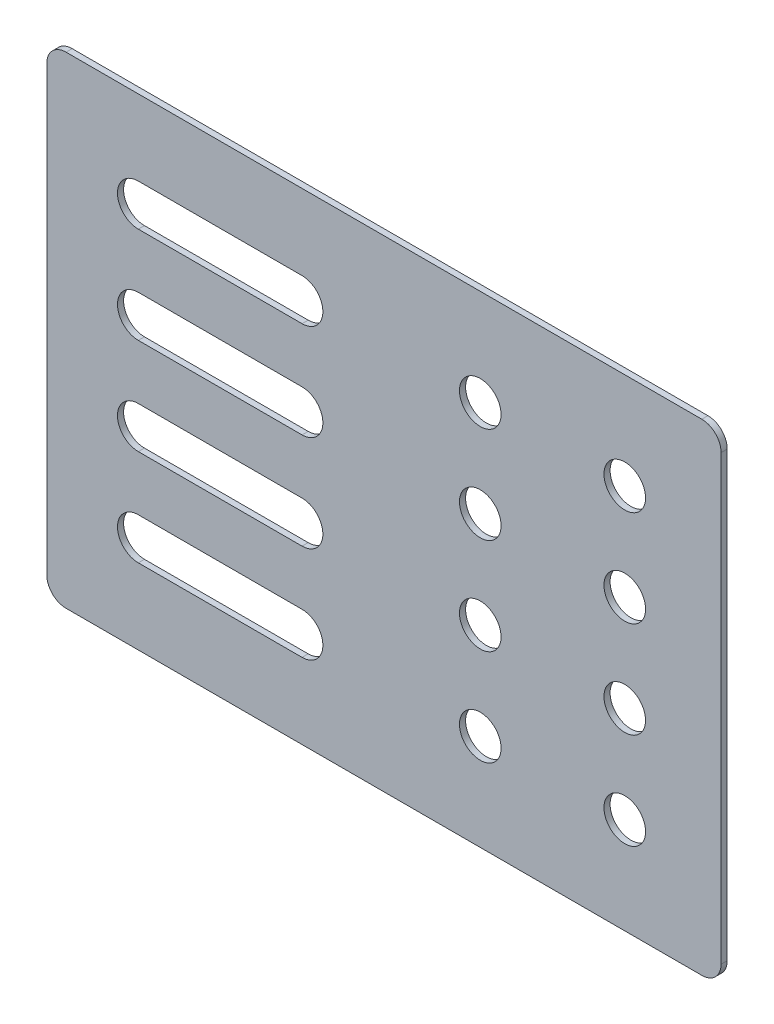
SolidWorks part; units mm, degrees
ref_plane "Front Plane" through (0, 0, 0) normal (0, 0, 1) x (1, 0, 0)
ref_plane "Top Plane" through (0, 0, 0) normal (0, 1, 0) x (1, 0, 0)
ref_plane "Right Plane" through (0, 0, 0) normal (1, 0, 0) x (0, 0, -1)
sketch "Sketch1" plane through (0, 0, 0) normal (0, 0, 1) x (1, 0, 0)
  line L0 (9.5, -10) -> (26.5, -10) construction
  line L1 (70, 0) -> (0, 0)
  line L2 (70, 0) -> (70, -50)
  line L3 (70, -50) -> (0, -50)
  line L4 (0, 0) -> (0, -50)
  line L9 (9.5, -7.84) -> (26.5, -7.84)
  line L12 (9.5, -12.16) -> (26.5, -12.16)
  line L13 (9.5, -22.16) -> (26.5, -22.16)
  line L14 (9.5, -17.84) -> (26.5, -17.84)
  line L15 (9.5, -20) -> (26.5, -20) construction
  line L16 (9.5, -32.16) -> (26.5, -32.16)
  line L17 (9.5, -27.84) -> (26.5, -27.84)
  line L18 (9.5, -30) -> (26.5, -30) construction
  line L19 (9.5, -42.16) -> (26.5, -42.16)
  line L20 (9.5, -37.84) -> (26.5, -37.84)
  line L21 (9.5, -40) -> (26.5, -40) construction
  circle A0 centre (45, -10) radius 2.16
  circle A1 centre (60, -10) radius 2.16
  circle A2 centre (20, -10) radius 2.16
  circle A3 centre (20, -20) radius 2.16
  circle A4 centre (45, -20) radius 2.16
  circle A5 centre (60, -20) radius 2.16
  circle A6 centre (20, -30) radius 2.16
  circle A7 centre (45, -30) radius 2.16
  circle A8 centre (60, -30) radius 2.16
  circle A9 centre (20, -40) radius 2.16
  circle A10 centre (45, -40) radius 2.16
  circle A11 centre (60, -40) radius 2.16
  circle A20 centre (45, -10) radius 3.9624 construction
  circle A21 centre (45, -20) radius 3.9624 construction
  arc A22 (9.5, -7.84) -> (9.5, -12.16) centre (9.5, -10) ccw
  arc A23 (26.5, -12.16) -> (26.5, -7.84) centre (26.5, -10) ccw
  arc A24 (9.5, -17.84) -> (9.5, -22.16) centre (9.5, -20) ccw
  arc A25 (26.5, -22.16) -> (26.5, -17.84) centre (26.5, -20) ccw
  arc A26 (9.5, -27.84) -> (9.5, -32.16) centre (9.5, -30) ccw
  arc A27 (26.5, -32.16) -> (26.5, -27.84) centre (26.5, -30) ccw
  arc A28 (9.5, -37.84) -> (9.5, -42.16) centre (9.5, -40) ccw
  arc A29 (26.5, -42.16) -> (26.5, -37.84) centre (26.5, -40) ccw
  point P8 (18, -10)
  point P40 (18, -20)
  point P47 (18, -30)
  point P54 (18, -40)
  dimension "D5" = 4.32
  dimension "D11" = 7.9248
  dimension "D1" = 10
  dimension "D2" = 15
  dimension "D3" = 70
  dimension "D4" = 10
  dimension "D6" = 25
  dimension "D7" = 10
  dimension "D8" = 10
  dimension "D10" = 2
  dimension "D12" = 17
  dimension "D13" = 10
  dimension "D9" = 4
extrude "Boss-Extrude1" add sketch "Sketch1" along normal blind 0.635 contours L1 L4 L3 L2 A11 A10 A9 L9 A2 A8 A7 A5 A4 A1 A0 region at (36.2997, -25, 0)
fillet "Fillet1" radius 2 4 edges at (70, -50, 0.3175) (0, -50, 0.3175) (70, 0, 0.3175) (0, 0, 0.3175)
